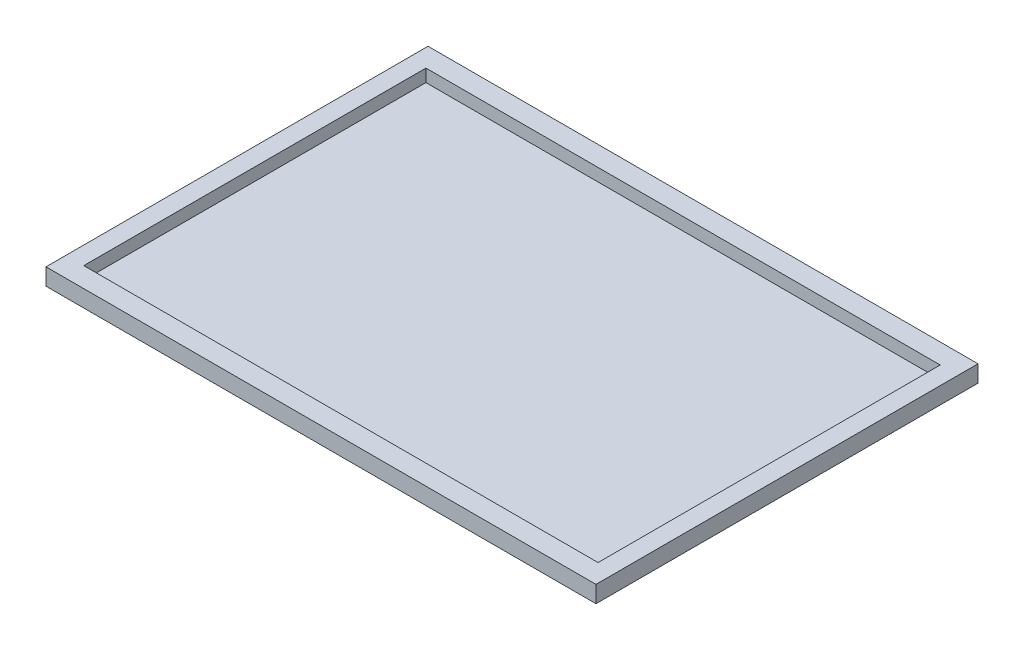
SolidWorks part; units mm, degrees
ref_plane "Front Plane" through (0, 0, 0) normal (0, 0, 1) x (1, 0, 0)
ref_plane "Top Plane" through (0, 0, 0) normal (0, 1, 0) x (1, 0, 0)
ref_plane "Right Plane" through (0, 0, 0) normal (1, 0, 0) x (0, 0, -1)
sketch "Sketch1" plane through (0, 0, 0) normal (0, 1, 0) x (1, 0, 0)
  line L1 (-65.5, -45.5) -> (65.5, -45.5)
  line L2 (-65.5, -45.5) -> (-65.5, 45.5)
  line L3 (-65.5, 45.5) -> (65.5, 45.5)
  line L4 (65.5, -45.5) -> (65.5, 45.5)
  line L5 (-65.5, -45.5) -> (65.5, 45.5) construction
  line L6 (-65.5, 45.5) -> (65.5, -45.5) construction
  point P0 (0, 0)
  dimension "D1" = 91
  dimension "D2" = 131
extrude "Boss-Extrude1" add sketch "Sketch1" along normal blind 4
sketch "Sketch2" plane through (0, 4, 0) normal (0, 1, 0) x (1, 0, 0)
  line L1 (-61.25, -40.75) -> (61.25, -40.75)
  line L2 (-61.25, -40.75) -> (-61.25, 40.75)
  line L3 (-61.25, 40.75) -> (61.25, 40.75)
  line L4 (61.25, -40.75) -> (61.25, 40.75)
  line L5 (-61.25, -40.75) -> (61.25, 40.75) construction
  line L6 (-61.25, 40.75) -> (61.25, -40.75) construction
  point P0 (0, 0)
  dimension "D1" = 81.5
  dimension "D2" = 122.5
extrude "Cut-Extrude1" cut sketch "Sketch2" against normal blind 3
